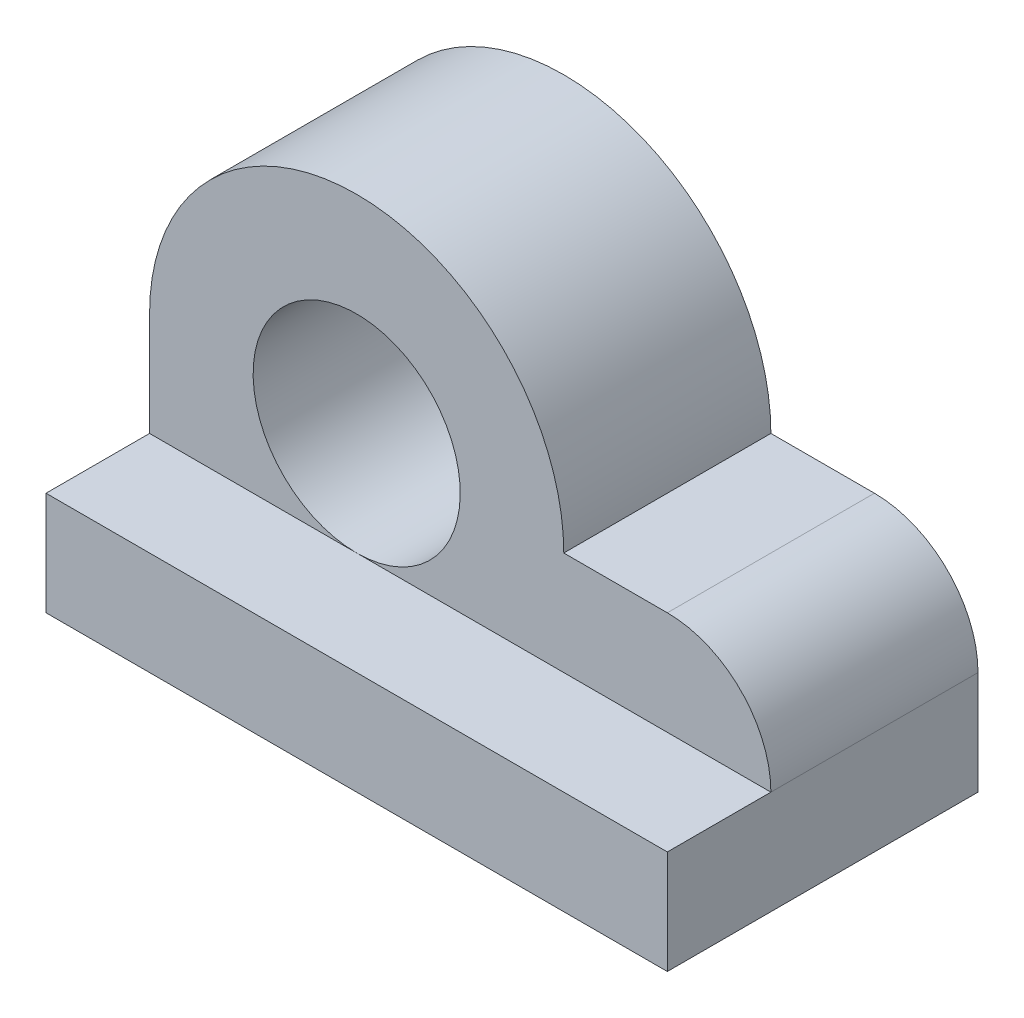
SolidWorks part; units mm, degrees
ref_plane "前基準面" through (0, 0, 0) normal (0, 0, 1) x (1, 0, 0)
ref_plane "上基準面" through (0, 0, 0) normal (0, 1, 0) x (1, 0, 0)
ref_plane "右基準面" through (0, 0, 0) normal (1, 0, 0) x (0, 0, -1)
sketch "草圖1" plane through (0, 0, 0) normal (0, 0, 1) x (1, 0, 0)
  line L0 (0, 0) -> (0, 15.5547) construction
  line L1 (0, 0) -> (-21.833, 0) construction
  line L2 (-10, 0) -> (-10, -10)
  line L3 (-10, -10) -> (20, -10)
  line L4 (20, -10) -> (20, -5)
  line L5 (15, 0) -> (10, 0)
  line L6 (-10, -5) -> (20, -5)
  circle A0 centre (0, 0) radius 5
  arc A1 (10, 0) -> (-10, 0) centre (0, 0) ccw
  arc A2 (20, -5) -> (15, 0) centre (15, -5) ccw
  dimension "D1" = 10
  dimension "D2" = 20
  dimension "D5" = 5
  dimension "D3" = 10
  dimension "D4" = 30
  dimension "D6" = 5
extrude "填料-伸長1" add sketch "草圖1" along normal blind 10 contours L6 A2 L5 A1 L2 A0 | L6 L2 L3 L4 region at (0, 9.6646, 0) region at (5, -7.5, 0)
extrude "填料-伸長2" add sketch "草圖1<3>" along normal blind 15 contours L6 L2 L3 L4 region at (5, -7.5, 0)
sketch "草圖1<3>" plane through (0, 0, 0) normal (0, 0, 1) x (1, 0, 0) same geometry as "草圖1"
